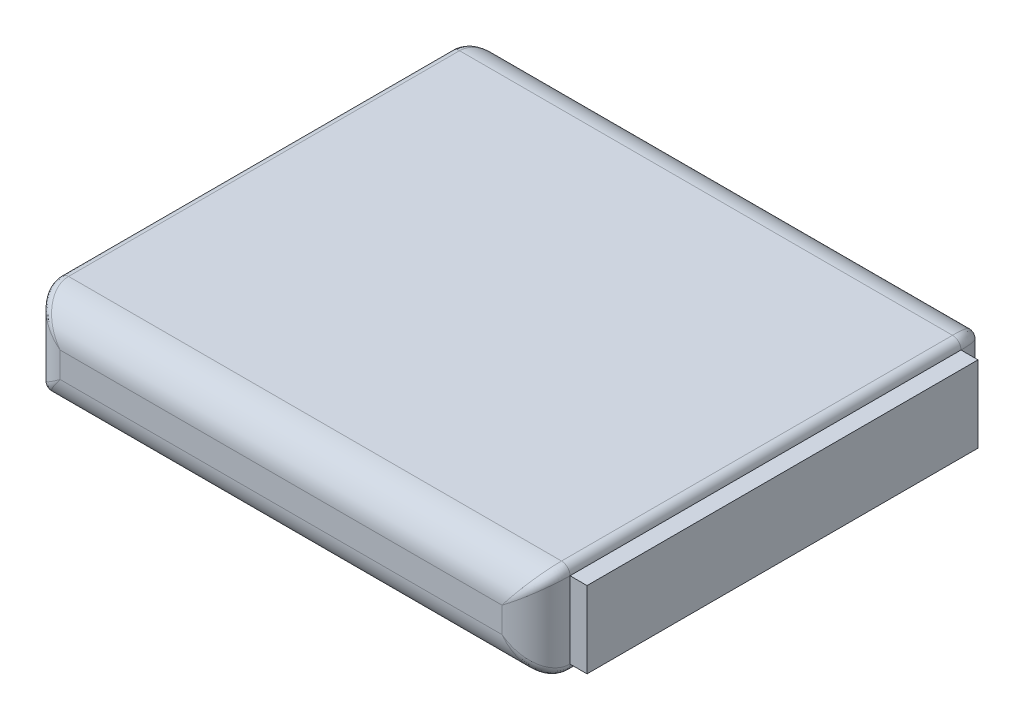
SolidWorks part; units mm, degrees
ref_plane "Front Plane" through (0, 0, 0) normal (0, 0, 1) x (1, 0, 0)
ref_plane "Top Plane" through (0, 0, 0) normal (0, 1, 0) x (1, 0, 0)
ref_plane "Right Plane" through (0, 0, 0) normal (1, 0, 0) x (0, 0, -1)
sketch "Sketch1" plane through (0, 0, 0) normal (0, 1, 0) x (1, 0, 0)
  line L1 (15.2444, -10.4273) -> (-14.7556, -10.4273)
  line L2 (15.2444, -10.4273) -> (15.2444, 16.5727)
  line L3 (15.2444, 16.5727) -> (-14.7556, 16.5727)
  line L4 (-14.7556, -10.4273) -> (-14.7556, 16.5727)
  dimension "D1" = 30
  dimension "D2" = 27
extrude "Boss-Extrude1" add sketch "Sketch1" along normal blind 5.5
fillet "Fillet1" radius 0.5 4 edges at (-14.7556, 0, -3.0727) (15.2444, 0, -3.0727) (15.2444, 5.5, -3.0727) (-14.7556, 5.5, -3.0727)
fillet "Fillet2" radius 2 16 edges at (-14.6092, 5.3536, 10.4273) (-14.7556, 2.75, 10.4273) (-14.6092, 0.1464, 10.4273) (15.098, 0.1464, 10.4273) (15.2444, 2.75, 10.4273) (15.098, 5.3536, 10.4273) (15.098, 5.3536, -16.5727) (15.2444, 2.75, -16.5727) (15.098, 0.1464, -16.5727) (-14.6092, 0.1464, -16.5727) (-14.7556, 2.75, -16.5727) (-14.6092, 5.3536, -16.5727) (0.2444, 0, 10.4273) (0.2444, 5.5, 10.4273) (0.2444, 0, -16.5727) (0.2444, 5.5, -16.5727)
sketch "Sketch2" plane through (15.2444, 0, 0) normal (1, 0, 0) x (0, 0, -1)
  line L1 (-8.4273, 5) -> (14.5727, 5)
  line L2 (-8.4273, 5) -> (-8.4273, 0.5)
  line L3 (-8.4273, 0.5) -> (14.5727, 0.5)
  line L4 (14.5727, 5) -> (14.5727, 0.5)
extrude "Boss-Extrude2" add sketch "Sketch2" along normal blind 1
